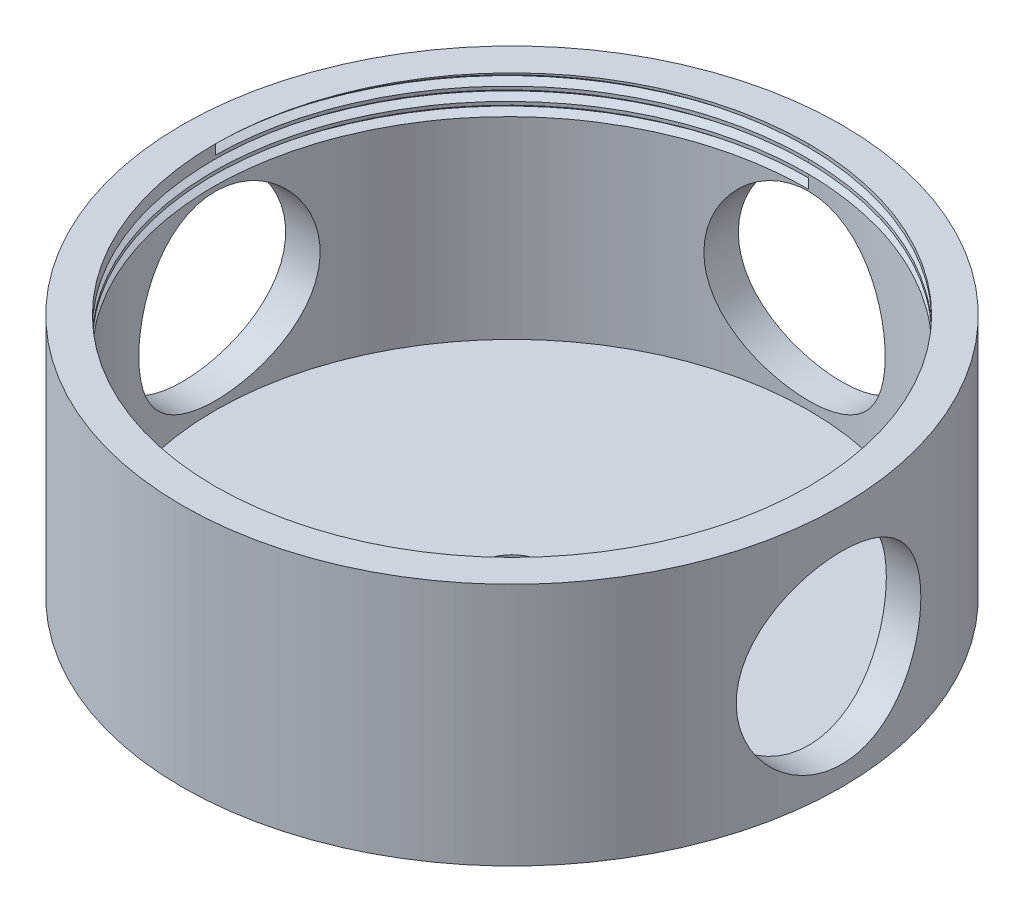
SolidWorks part; units mm, degrees
ref_plane "Front Plane" through (0, 0, 0) normal (0, 0, 1) x (1, 0, 0)
ref_plane "Top Plane" through (0, 0, 0) normal (0, 1, 0) x (1, 0, 0)
ref_plane "Right Plane" through (0, 0, 0) normal (1, 0, 0) x (0, 0, -1)
sketch "Sketch1" plane through (0, 0, 0) normal (0, 1, 0) x (1, 0, 0)
  circle A0 centre (0, 0) radius 50
  dimension "D1" = 100
extrude "Boss-Extrude1" add sketch "Sketch1" along normal blind 2 contours A0
sketch "Sketch2" plane through (0, 2, 0) normal (0, 1, 0) x (1, 0, 0)
  circle A0 centre (0, 0) radius 50
  circle A1 centre (0, 0) radius 45
  dimension "D1" = 100
  dimension "D2" = 5
extrude "Boss-Extrude2" add sketch "Sketch2" along normal blind 35
ref_plane "Plane3" through (0, 0, 40) normal (0, 0, 1) x (1, 0, 0)
sketch "Sketch5" plane through (0, 0, 40) normal (0, 0, 1) x (1, 0, 0)
  line L0 (-50, 0) -> (50, 0) construction
  line L1 (-26.6422, 0) -> (27.3578, 0)
  line L2 (-26.6422, 0) -> (-26.6422, -34)
  line L3 (-26.6422, -34) -> (27.3578, -34)
  line L4 (27.3578, 0) -> (27.3578, -34)
  line L5 (-50, 0) -> (50, 0) construction
  line L6 (-24.6422, -2) -> (25.3578, -2)
  line L7 (-24.6422, -2) -> (-24.6422, -32)
  line L8 (-24.6422, -32) -> (25.3578, -32)
  line L9 (25.3578, -2) -> (25.3578, -32)
  dimension "D1" = 2
  dimension "D2" = 2
  dimension "D3" = 2
  dimension "D4" = 2
  dimension "D5" = 50
  dimension "D6" = 2
  dimension "D7" = 30
thread "Thread1" pitch 2 method cut profile "Thread Profile1" start angle 0, offset 0, length 4.5, pitch 2, diameter 90
ref_plane "Plane4" through (-45, 37, 0) normal (0, 0, 1) x (-1, 0, 0)
sketch "Thread Profile1" plane through (-45, 37, 0) normal (0, 0, 1) x (-1, 0, 0)
  line L0 (0, 0) -> (0, 2) construction
  line L1 (0, 0) -> (1.0825, 0.625)
  line L2 (1.0825, 0.625) -> (1.0825, 0.875)
  line L3 (1.0825, 0.875) -> (0, 1.5)
  line L4 (1.0825, 0.75) -> (0, 0.75) construction
  line L11 (0, 0) -> (0, 1.5)
  point P2 (0, 0)
  dimension "Pitch" = 2
  dimension "Profile_Angle" = 60
  dimension "Profile_Land" = 0.25
  dimension "Profile_Height" = 1.0825
ref_plane "Plane6" through (0, 0, -50) normal (0, 0, -1) x (-1, 0, 0)
sketch "Sketch10" plane through (0, 0, -50) normal (0, 0, -1) x (-1, 0, 0)
  line L0 (0, 17) -> (-42.3594, 17) construction
  line L1 (0, 37) -> (0, 0) construction
  line L2 (50, 37) -> (-50, 37) construction
  line L3 (-42.3594, 17) -> (37.1989, 17) construction
  circle A1 centre (0, 17) radius 13.75
  point P0 (-0.3373, 18)
  point P4 (0, 0)
  dimension "D2" = 27.5
  dimension "D5" = 37
  dimension "D6" = 20
extrude "Cut-Extrude2" cut sketch "Sketch10" against normal up to next
ref_plane "Plane8" through (-50, 0, 0) normal (-1, 0, 0) x (0, 0, 1)
sketch "Sketch12" plane through (-50, 0, 0) normal (-1, 0, 0) x (0, 0, 1)
  line L1 (50, 37) -> (-50, 37) construction
  circle A0 centre (0, 17) radius 13.75
  dimension "D1" = 27.5
  dimension "D2" = 20
extrude "Cut-Extrude4" cut sketch "Sketch12" against normal up to next
ref_plane "Plane9" through (50, 0, 0) normal (1, 0, 0) x (0, 0, -1)
sketch "Sketch13" plane through (50, 0, 0) normal (1, 0, 0) x (0, 0, -1)
  line L0 (50, 37) -> (-50, 37) construction
  circle A0 centre (0, 17) radius 14
  dimension "D1" = 28
  dimension "D2" = 20
extrude "Cut-Extrude5" cut sketch "Sketch13" against normal up to next
sketch "Sketch14" plane through (0, 2, 0) normal (0, 1, 0) x (1, 0, 0)
  circle A0 centre (0, 0) radius 5
  point P3 (0, 0)
  dimension "D1" = 10
extrude "Cut-Extrude6" cut sketch "Sketch14" against normal up to next
